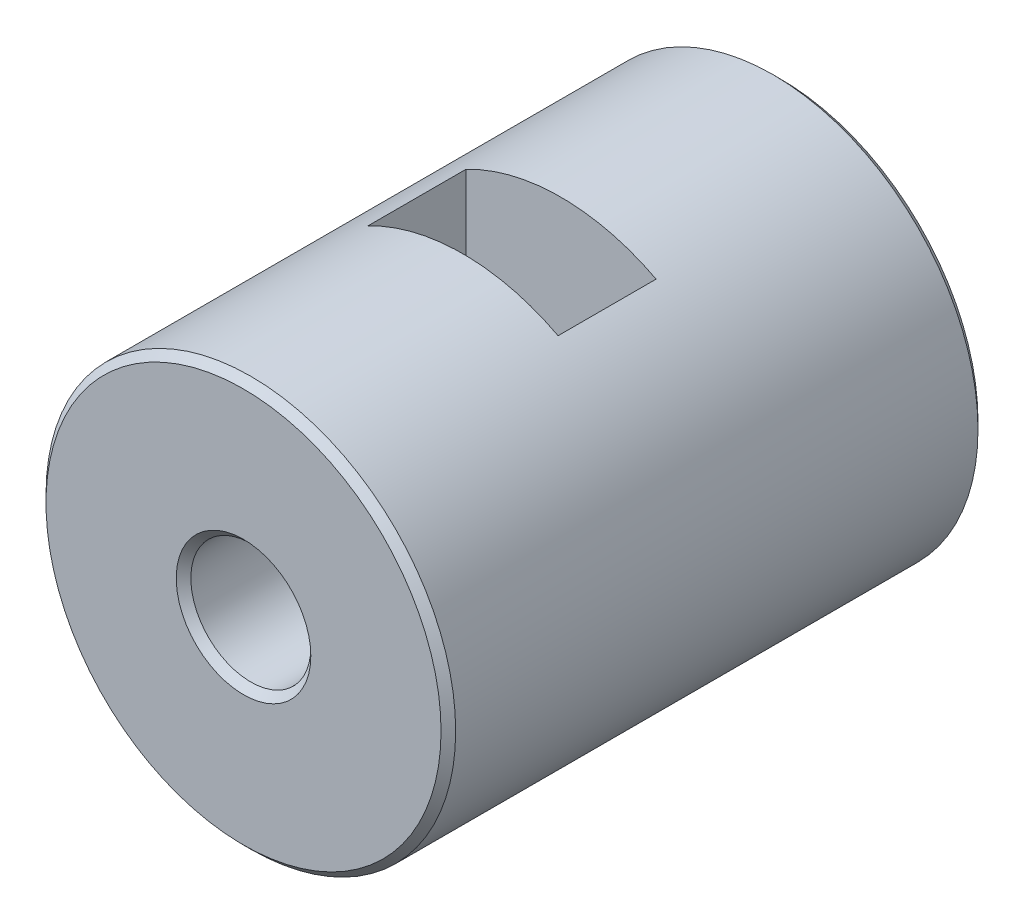
SolidWorks part; units mm, degrees
ref_plane "Front Plane" through (0, 0, 0) normal (0, 0, 1) x (1, 0, 0)
ref_plane "Top Plane" through (0, 0, 0) normal (0, 1, 0) x (1, 0, 0)
ref_plane "Right Plane" through (0, 0, 0) normal (1, 0, 0) x (0, 0, -1)
sketch "Sketch1" plane through (0, 0, 0) normal (0, 0, 1) x (1, 0, 0)
  circle A0 centre (0, 0) radius 14
  dimension "D1" = 28
extrude "Boss-Extrude1" add sketch "Sketch1" along normal blind 15
sketch "Sketch2" plane through (0, 0, 15) normal (0, 0, 1) x (1, 0, 0)
  line L0 (0, 14) -> (0, -14) construction
  line L1 (-6.5, 3.7528) -> (-6.5, 12.3996)
  line L3 (-6.5, 3.7528) -> (-6.5, -3.7528)
  line L4 (-6.5, -3.7528) -> (0, -7.5056)
  line L5 (0, -7.5056) -> (6.5, -3.7528)
  line L6 (6.5, -3.7528) -> (6.5, 3.7528)
  line L8 (6.5, 3.7528) -> (6.5, 12.3996)
  line L10 (6.5, 3.7528) -> (3.25, 5.6292) [skipped]
  line L11 (-3.25, 5.6292) -> (-6.5, 3.7528) [skipped]
  circle A0 centre (0, 0) radius 14 construction
  circle A1 centre (0, 0) radius 6.5 construction
  circle A3 centre (0, 0) radius 14
  arc A4 (-6.5, 12.3996) -> (6.5, 12.3996) centre (0, 0) ccw
  dimension "D1" = 13
  dimension "D2" = 0
extrude "Boss-Extrude2" add sketch "Sketch2" along normal blind 6.7
sketch "Sketch3" plane through (0, 0, 21.7) normal (0, 0, 1) x (1, 0, 0)
  arc A0 (6.5, 12.3996) -> (-6.5, 12.3996) centre (0, 0) ccw construction
  arc A1 (-6.5, 12.3996) -> (6.5, 12.3996) centre (0, 0) ccw construction
  arc A2 (6.5, 12.3996) -> (-6.5, 12.3996) centre (0, 0) ccw
  arc A3 (-6.5, 12.3996) -> (6.5, 12.3996) centre (0, 0) ccw
extrude "Boss-Extrude3" add sketch "Sketch3" along normal blind 15
sketch "Sketch4" plane through (0, 0, 36.7) normal (0, 0, 1) x (1, 0, 0)
  circle A0 centre (0, 0) radius 4.1
  dimension "D1" = 8.2
extrude "Cut-Extrude1" cut sketch "Sketch4" against normal through all
chamfer "Chamfer1" distance 0.5 angle 45 4 edges at (14, 0, 0) (4.1, 0, 0) (14, 0, 36.7) (4.1, 0, 36.7)
